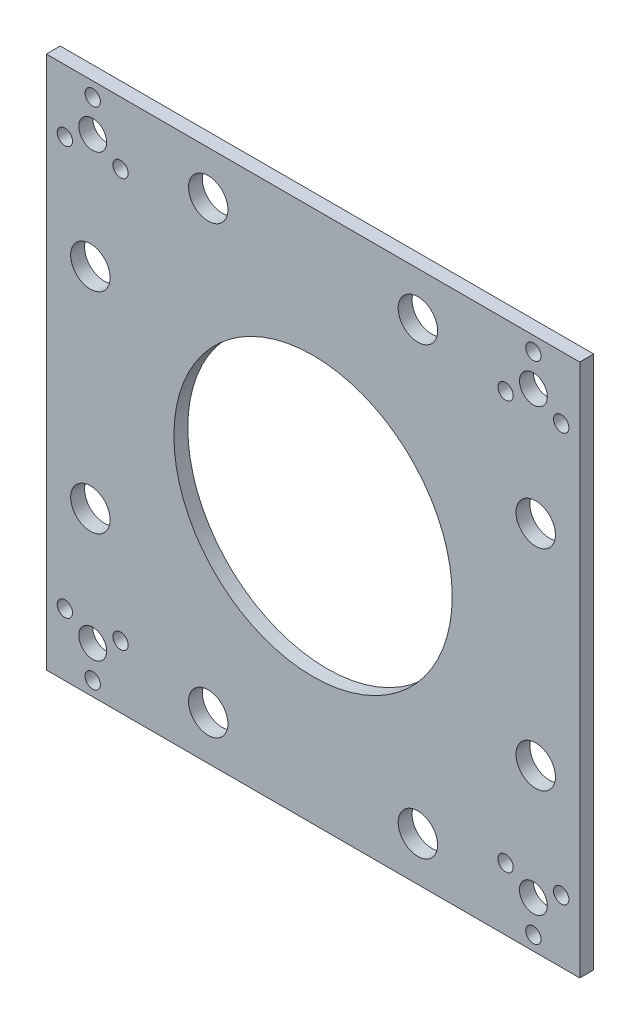
SolidWorks part; units mm, degrees
ref_plane "前视基准面" through (0, 0, 0) normal (0, 0, 1) x (1, 0, 0)
ref_plane "上视基准面" through (0, 0, 0) normal (0, 1, 0) x (1, 0, 0)
ref_plane "右视基准面" through (0, 0, 0) normal (1, 0, 0) x (0, 0, -1)
other "Configuration Table"
sketch "草图1" plane through (0, 0, 0) normal (0, 0, 1) x (1, 0, 0)
  line L1 (-57.5, 57.5) -> (57.5, 57.5)
  line L2 (-57.5, 57.5) -> (-57.5, -57.5)
  line L3 (-57.5, -57.5) -> (57.5, -57.5)
  line L4 (57.5, 57.5) -> (57.5, -57.5)
  line L5 (-57.5, 57.5) -> (57.5, -57.5) construction
  line L6 (-57.5, -57.5) -> (57.5, 57.5) construction
  line L7 (-47.5, -47.5) -> (47.5, -47.5) construction
  line L8 (-47.5, -47.5) -> (-47.5, 47.5) construction
  line L9 (-47.5, 47.5) -> (47.5, 47.5) construction
  line L10 (47.5, -47.5) -> (47.5, 47.5) construction
  line L11 (-47.5, -47.5) -> (47.5, 47.5) construction
  line L12 (-47.5, 47.5) -> (47.5, -47.5) construction
  circle A0 centre (0, 0) radius 30
  circle A1 centre (-47.5, 47.5) radius 3
  circle A2 centre (47.5, 47.5) radius 3
  circle A3 centre (47.5, -47.5) radius 3
  circle A4 centre (-47.5, -47.5) radius 3
  point P0 (0, 0)
  dimension "D3" = 60
  dimension "D6" = 6
  dimension "D1" = 115
  dimension "D2" = 115
  dimension "D4" = 95
  dimension "D5" = 95
extrude "凸台-拉伸1" add sketch "草图1" along normal blind 3
sketch "草图3" plane through (0, 0, 3) normal (0, 0, 1) x (1, 0, 0)
  line L1 (-47.5, 54.4282) -> (-53.5, 44.0359)
  line L2 (-53.5, 44.0359) -> (-41.5, 44.0359)
  line L3 (-41.5, 44.0359) -> (-47.5, 54.4282)
  circle A0 centre (-47.5, 47.5) radius 3.4641 construction
  circle A1 centre (-41.5, 44.0359) radius 1.65
  circle A2 centre (-53.5, 44.0359) radius 1.65
  circle A3 centre (-47.5, 54.4282) radius 1.65
  dimension "D3" = 3.3
  dimension "D1" = 12
extrude "切除-拉伸2" cut sketch "草图3" against normal through all contours L1 A2 L2 | L2 A1 L3 | L3 A1 L2 | L2 A2 L1 | L3 A3 L1 | L1 A3 L3 region at (-47.5, 53.3778, 3) region at (-47.5, 54.6383, 3) region at (-52.5903, 44.5611, 3) region at (-53.6819, 43.9309, 3) region at (-41.3181, 43.9309, 3) region at (-42.4097, 44.5611, 3)
mirror "镜向3" about plane through (0, 0, 0) normal (1, 0, 0) of "切除-拉伸2"
mirror "镜向4" about plane through (0, 0, 0) normal (0, 1, 0) of "镜向3"
sketch "草图4" plane through (0, 0, 3) normal (0, 0, 1) x (1, 0, 0)
  line L0 (0, 57.5) -> (0, -57.5) construction
  line L1 (57.5, 57.5) -> (-57.5, 57.5) construction
  line L2 (-57.5, -57.5) -> (57.5, -57.5) construction
  line L3 (-57.5, 0) -> (57.5, 0) construction
  line L4 (-57.5, 57.5) -> (-57.5, -57.5) construction
  line L5 (57.5, -57.5) -> (57.5, 57.5) construction
  circle A0 centre (-22.6, 48) radius 4.25
  circle A1 centre (-48, 22.6) radius 4.25
  circle A2 centre (22.6, 48) radius 4.25
  circle A3 centre (48, 22.6) radius 4.25
  circle A4 centre (48, -22.6) radius 4.25
  circle A5 centre (22.6, -48) radius 4.25
  circle A6 centre (-48, -22.6) radius 4.25
  circle A7 centre (-22.6, -48) radius 4.25
  dimension "D1" = 45.2
  dimension "D2" = 96
  dimension "D3" = 8.5
  dimension "D4" = 8.5
  dimension "D5" = 96
  dimension "D6" = 45.2
extrude "切除-拉伸3" cut sketch "草图4" against normal up to surface (3 mm away) up to face at (-39.85, -44.0359, 0)
